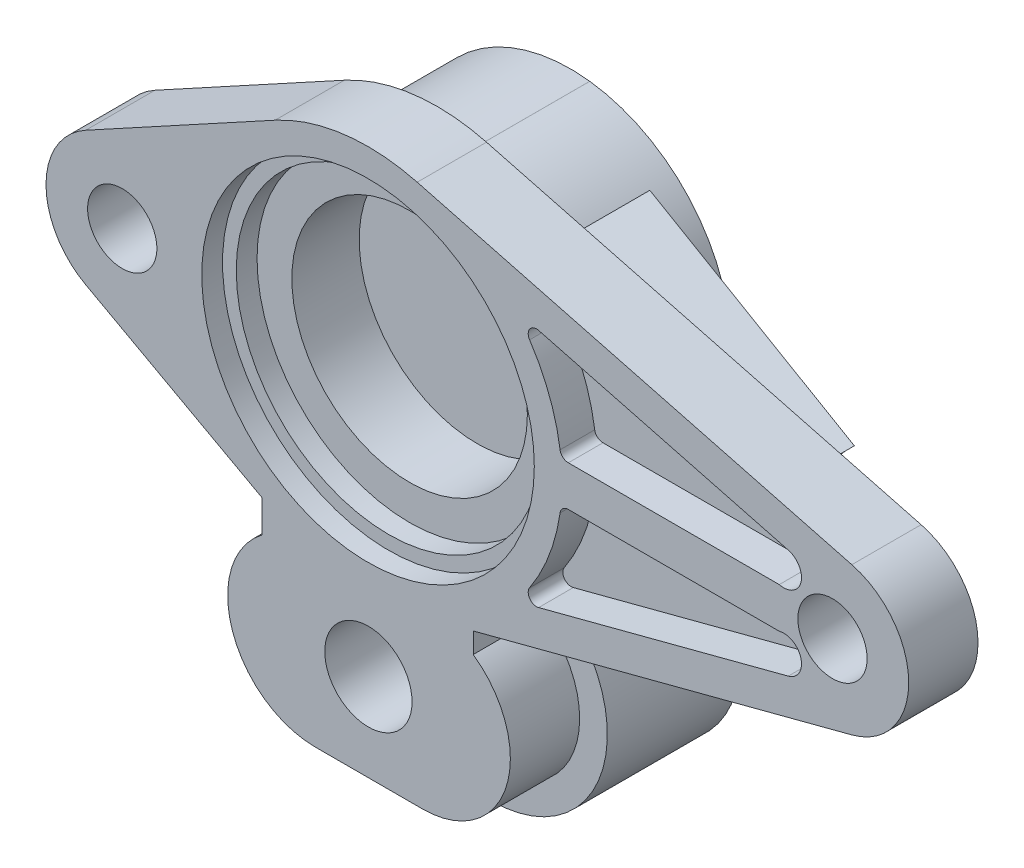
SolidWorks part; units mm, degrees
ref_plane "Front Plane" through (0, 0, 0) normal (0, 0, 1) x (1, 0, 0)
ref_plane "Top Plane" through (0, 0, 0) normal (0, 1, 0) x (1, 0, 0)
ref_plane "Right Plane" through (0, 0, 0) normal (1, 0, 0) x (0, 0, -1)
sketch "Sketch1" plane through (0, 0, 0) normal (0, 0, 1) x (1, 0, 0)
  line L0 (-25.8766, -6.131) -> (-6.8556, -16.5143)
  line L1 (-4.8358, -32.3088) -> (5.0194, -32.3088)
  line L2 (7.0796, -16.5249) -> (44.3417, -6.7567)
  line L3 (44.3417, 6.7567) -> (-2.3215, 18.9894)
  line L4 (-2.3215, 18.9894) -> (-25.8766, 6.131)
  arc A0 (-6.8556, -16.5143) -> (-4.8358, -32.3088) centre (-4.8358, -24.2824) ccw
  arc A1 (5.0194, -32.3088) -> (7.0796, -16.5249) centre (5.0194, -24.2824) ccw
  arc A2 (44.3417, -6.7567) -> (44.3417, 6.7567) centre (42.5704, 0) ccw
  arc A3 (-25.8766, 6.131) -> (-25.8766, -6.131) centre (-22.5298, 0) ccw
extrude "Boss-Extrude1" add sketch "Sketch1" against normal blind 6.35
sketch "Sketch2" plane through (0, 0, -6.35) normal (0, 0, -1) x (-1, 0, 0)
  line L0 (4.8358, -34.8488) -> (-5.0194, -34.8488)
  line L1 (-14.0618, -18.8158) -> (-14.0618, -4.2193)
  line L2 (-1.7812, 14.5727) -> (-1.7783, 14.5731)
  line L3 (13.8782, -4.7889) -> (13.8782, -18.8158)
  arc A0 (13.8782, -18.8158) -> (4.8358, -34.8488) centre (4.8358, -24.2824) cw
  arc A1 (-5.0194, -34.8488) -> (-14.0618, -18.8158) centre (-5.0194, -24.2824) cw
  arc A2 (-14.0618, -4.2193) -> (-1.7812, 14.5727) centre (0, 0) cw
  arc A3 (-1.7783, 14.5731) -> (13.8782, -4.7889) centre (0, 0) cw
extrude "Boss-Extrude2" add sketch "Sketch2" along normal blind 12.192
ref_plane "Plane1" through (5.0846, 0, -17.4922) normal (0.2791, 0, -0.9603) x (0, 1, 0)
sketch "Sketch4" plane through (0, 0, -6.35) normal (0, 0, -1) x (-1, 0, 0)
  line L0 (-36.0927, 7.8272) -> (-9.6638, 11.0521)
  line L1 (-14.0618, -4.2193) -> (-14.0618, -10.5126)
  line L2 (-14.0618, -10.5126) -> (-36.0847, -7.8206)
  arc A0 (-9.6638, 11.0521) -> (-14.0618, -4.2193) centre (0, 0) ccw
  arc A1 (-36.0847, -7.8206) -> (-36.0927, 7.8272) centre (-42.5704, 0) ccw
extrude "Boss-Extrude3" add sketch "Sketch4" along normal up to surface up to plane "Plane1"
sketch "Sketch5" plane through (0, 0, 0) normal (0, 0, 1) x (1, 0, 0)
  line L0 (17.6833, 1.8521) -> (37.6894, 1.8521)
  line L1 (38.5151, 5.0018) -> (15.6363, 10.9995)
  arc A0 (37.6894, 1.8521) -> (38.5151, 5.0018) centre (38.1022, 3.427) ccw
  arc A1 (15.6363, 10.9995) -> (14.8085, 9.8406) centre (15.4431, 10.2624) ccw
  arc A2 (14.8085, 9.8406) -> (17.6833, 1.8521) centre (0, 0) cw
extrude "Cut-Extrude1" cut sketch "Sketch5" against normal blind 3.175
sketch "Sketch6" plane through (0, 0, 0) normal (0, 0, 1) x (1, 0, 0)
  line L0 (15.6363, -10.9995) -> (38.5151, -5.0018)
  line L1 (37.6894, -1.8521) -> (17.6833, -1.8521)
  arc A0 (38.5151, -5.0018) -> (37.6894, -1.8521) centre (38.1022, -3.427) ccw
  arc A1 (17.6833, -1.8521) -> (14.8085, -9.8406) centre (0, 0) cw
  arc A2 (14.8085, -9.8406) -> (15.6363, -10.9995) centre (15.4431, -10.2624) ccw
extrude "Cut-Extrude2" cut sketch "Sketch6" against normal blind 3.175
sketch "Sketch7" plane through (0, 0, 0) normal (0, 1, 0) x (1, 0, 0)
  line L0 (10.795, 9.9822) -> (0, 9.9822)
  line L1 (0, 9.9822) -> (0, 0)
  line L2 (0, 0) -> (15.24, 0)
  line L3 (15.24, 0) -> (15.24, 1.905)
  line L4 (15.24, 1.905) -> (13.9827, 1.905)
  line L5 (13.9827, 1.905) -> (13.9827, 3.81)
  line L6 (13.9827, 3.81) -> (10.795, 3.81)
  line L7 (10.795, 3.81) -> (10.795, 9.9822)
  line L8 (0, 9.9822) -> (0, 0) construction
revolve "Cut-Revolve1" cut sketch "Sketch7" angle 360 about L8 reverse direction yes
hole_wizard "Ø8.0 (8) Diameter Hole1" positions "Sketch9" profile "Sketch8" hole size "Ø8.0" standard "ANSI Metric"
sketch "Sketch9" plane through (0, 0, 0) normal (0, 0, 1) x (1, 0, 0)
  point P0 (0.0346, -24.2824)
sketch "Sketch8" plane through (0.0346, -24.2824, 0) normal (1, 0, 0) x (0, -1, 0)
  line L0 (0, 0) -> (0, 18.542)
  line L1 (0, 18.542) -> (4, 18.542)
  line L2 (4, 18.542) -> (4, 0)
  line L5 (4, 0) -> (0, 0)
  line L11 (0, -6.35) -> (0, 107.95) construction
  dimension "Thru Hole Dia." = 8
  dimension "Thru Hole Depth" = 18.542
hole_wizard "Hole1" positions "Sketch11" profile "Sketch10" legacy
sketch "Sketch11" plane through (0, 0, -6.35) normal (0, 0, -1) x (-1, 0, 0)
  point P0 (-42.5704, 0)
  point P1 (22.5298, 0)
sketch "Sketch10" plane through (42.5704, 0, -6.35) normal (1, 0, 0) x (0, 1, 0)
  line L0 (0, 0) -> (0, 6.35)
  line L1 (0, 6.35) -> (3.175, 6.35)
  line L2 (3.175, 6.35) -> (3.175, 0)
  line L3 (3.175, 0) -> (0, 0)
  line L4 (0, 110) -> (0, -10) construction
  dimension "Diameter" = 6.35
  dimension "Depth" = 6.35
chamfer "Chamfer1" distance 3.2561 angle 61.371 1 edges at (-6.8556, -16.5143, -3.175) first distance on face at (-15.8685, -11.5943, -3.81)
chamfer "Chamfer2" distance 2.6514 angle 75.311 1 edges at (7.0796, -16.5249, -3.175) first distance on face at (23.3809, -12.2515, -3.81)
fillet "Fillet1" radius 0.762 2 edges at (17.6833, -1.8521, -1.5875) (17.6833, 1.8521, -1.5875) tangent propagation no
fillet "Fillet2" radius 17.78 1 edges at (-2.3215, 18.9894, -3.175) tangent propagation no
